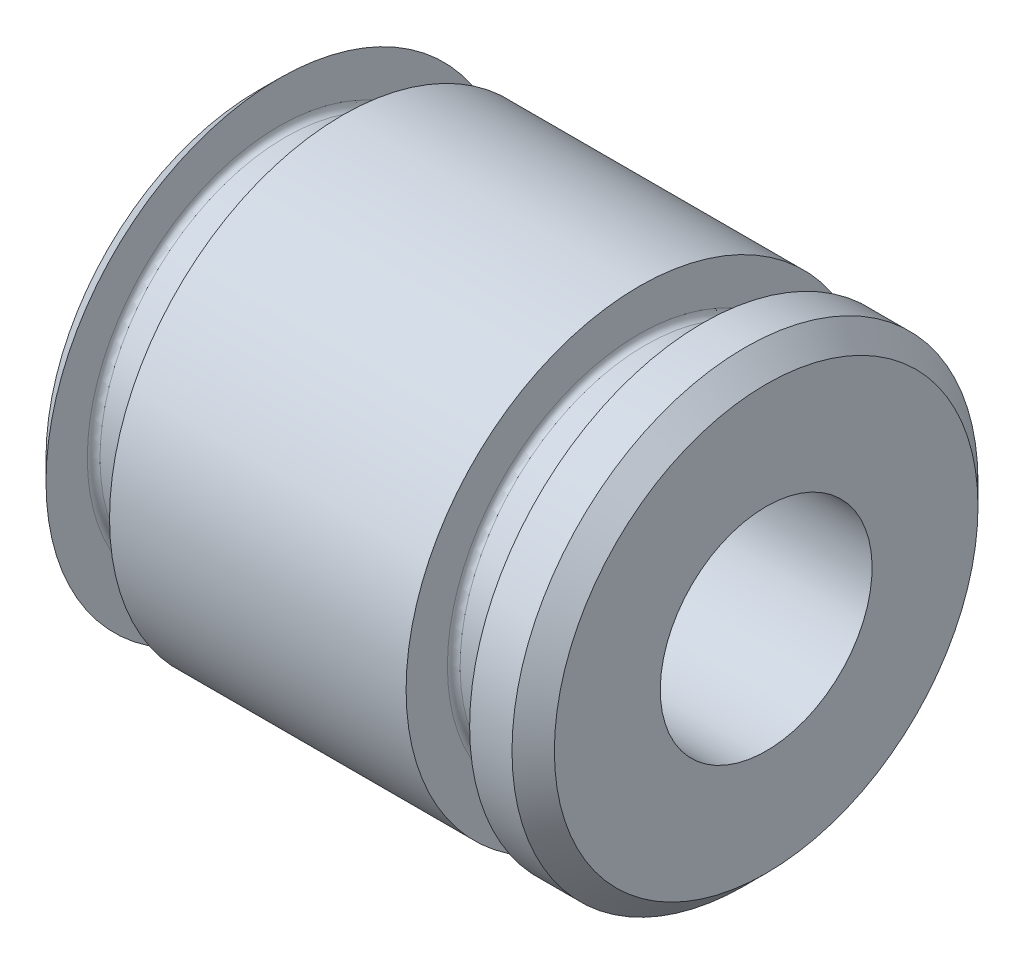
SolidWorks part; units mm, degrees
material "Acciaio al carbonio semplice"
ref_plane "Piano frontale" through (0, 0, 0) normal (0, 0, 1) x (1, 0, 0)
ref_plane "Piano superiore" through (0, 0, 0) normal (0, 1, 0) x (1, 0, 0)
ref_plane "Piano destro" through (0, 0, 0) normal (1, 0, 0) x (0, 0, -1)
sketch "Schizzo1" plane through (0, 0, 0) normal (0, 0, 1) x (1, 0, 0)
  line L0 (0, 0) -> (0, 11)
  line L2 (24, 11) -> (24, 0)
  line L3 (24, 0) -> (0, 0) construction
  line L8 (21, 11) -> (24, 11)
  line L9 (0, 0) -> (24, 0) construction
  line L10 (18, 11) -> (18, 8.75)
  line L11 (18, 8.75) -> (21, 8.75)
  line L12 (21, 8.75) -> (21, 11)
  line L13 (24, 0) -> (0, 0)
  line L15 (1, 8.75) -> (4, 8.75)
  line L16 (4, 8.75) -> (4, 11)
  line L17 (4, 11) -> (18, 11)
  line L18 (0, 11) -> (1, 11)
  line L19 (1, 11) -> (1, 8.75)
  line L20 (0, 0) -> (-4.0571, 0) construction
  dimension "D1" = 17.5
  dimension "D2" = 3
  dimension "D3" = 3
  dimension "D4" = 22
  dimension "D5" = 24
  dimension "D6" = 1
revolve "Rivoluzione1" add sketch "Schizzo1" angle 360 about L3
sketch "Schizzo2" plane through (24, 0, 0) normal (1, 0, 0) x (0, 0, -1)
  circle A0 centre (0, 0) radius 5
  dimension "D1" = 10
extrude "Taglio-Estrusione1" cut sketch "Schizzo2" against normal blind 21
chamfer "Smusso1" distance 1 angle 45 2 edges at (24, 11, 0) (0, 11, 0)
fillet "Raccordo1" radius 0.3 4 edges at (21, 8.75, 0) (18, 8.75, 0) (4, 8.75, 0) (1, 8.75, 0)
